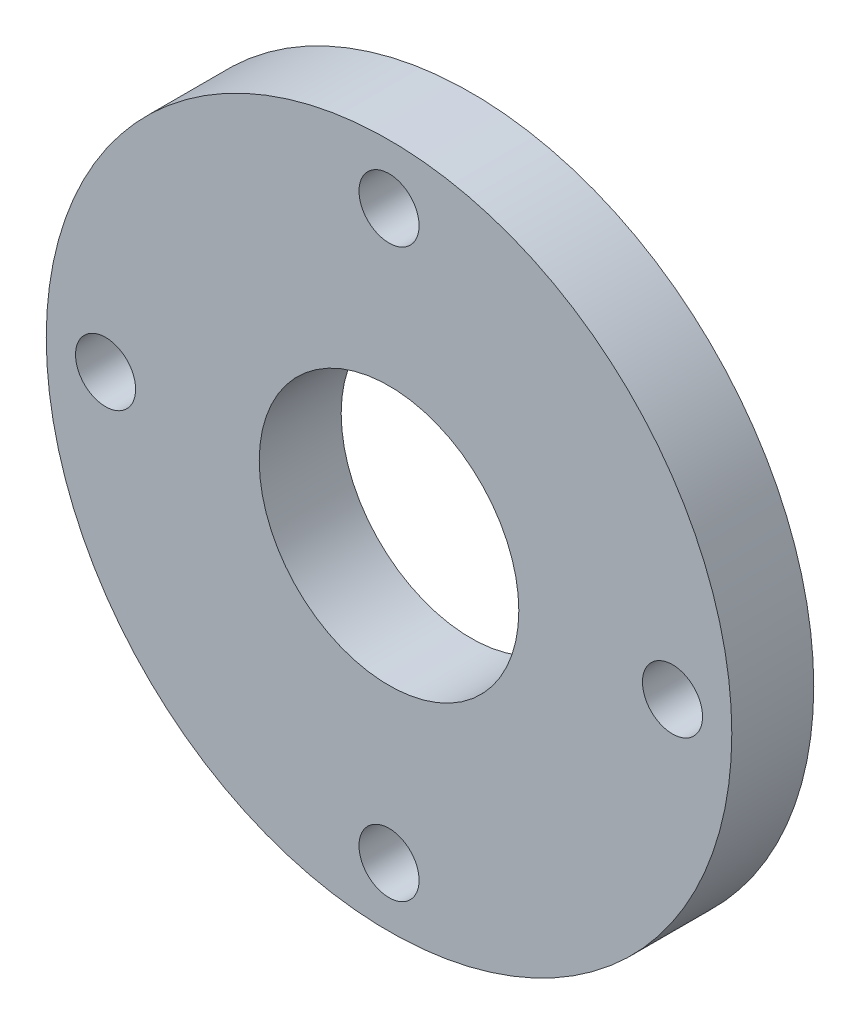
SolidWorks part; units mm, degrees
ref_plane "Front Plane" through (0, 0, 0) normal (0, 0, 1) x (1, 0, 0)
ref_plane "Top Plane" through (0, 0, 0) normal (0, 1, 0) x (1, 0, 0)
ref_plane "Right Plane" through (0, 0, 0) normal (1, 0, 0) x (0, 0, -1)
sketch "Sketch1" plane through (0, 0, 0) normal (1, 0, 0) x (0, 0, -1)
  line L0 (-103, -9.5) -> (-149, -9.5)
  line L5 (-1000, 0) -> (49000, 0)
  line L6 (0, -9.5) -> (0, 9.5)
  line L13 (0, 9.5) -> (-46.4, 9.5)
  line L26 (-46.4, 9.5) -> (-46.4, 14)
  line L27 (-46.4, 14) -> (-103, 14)
  line L32 (-103, 14) -> (-103, 9.5)
  line L34 (-165, 7) -> (-165, -7)
  line L36 (-103, -9.5) -> (-103, -14)
  line L37 (-103, -14) -> (-46.4, -14)
  line L38 (-46.4, -14) -> (-46.4, -9.5)
  line L39 (0, -9.5) -> (-46.4, -9.5)
  line L40 (-24.625, 37.6491) -> (-15.625, 37.6491)
  line L41 (-119.6, 22.6187) -> (-103, 22.6187)
  line L42 (-119.6, 22.6187) -> (-119.6, -22.6187)
  line L43 (-119.6, -22.6187) -> (-103, -22.6187)
  line L44 (-103, 22.6187) -> (-103, -22.6187)
  line L45 (-119.6, 22.6187) -> (-103, -22.6187) construction
  line L46 (-119.6, -22.6187) -> (-103, 22.6187) construction
  line L47 (-29.8, 22.6187) -> (-46.4, 22.6187)
  line L48 (-29.8, 22.6187) -> (-29.8, -22.6187)
  line L49 (-29.8, -22.6187) -> (-46.4, -22.6187)
  line L50 (-46.4, 22.6187) -> (-46.4, -22.6187)
  line L51 (-29.8, 22.6187) -> (-46.4, -22.6187) construction
  line L52 (-29.8, -22.6187) -> (-46.4, 22.6187) construction
  line L59 (-15.625, 37.6491) -> (-15.625, -37.6491)
  line L60 (-15.625, -37.6491) -> (-24.625, -37.6491)
  line L61 (-24.625, -22.6187) -> (-26.625, -22.6187)
  line L62 (-26.625, -22.6187) -> (-26.625, -12.5)
  line L63 (-26.625, -12.5) -> (-24.625, -12.5)
  line L64 (-24.625, -12.5) -> (-24.625, 12.5)
  line L65 (-24.625, 12.5) -> (-26.625, 12.5)
  line L66 (-26.625, 12.5) -> (-26.625, 22.6187)
  line L67 (-26.625, 22.6187) -> (-24.625, 22.6187)
  line L68 (-24.625, 22.6187) -> (-24.625, 37.6491)
  line L69 (-24.625, -22.6187) -> (-24.625, -37.6491)
  line L71 (-131.284, 37.6491) -> (-25.625, 37.6491)
  line L72 (-131.284, 37.6491) -> (-131.284, -37.6491)
  line L73 (-131.284, -37.6491) -> (-25.625, -37.6491)
  line L74 (-25.625, 37.6491) -> (-25.625, -37.6491)
  line L75 (-131.284, 37.6491) -> (-25.625, -37.6491) construction
  line L76 (-131.284, -37.6491) -> (-25.625, 37.6491) construction
  line L77 (-149, -9.5) -> (-149, -7)
  line L78 (-149, -7) -> (-165, -7)
  line L79 (-103, 9.5) -> (-149, 9.5)
  line L80 (-149, 7) -> (-165, 7)
  line L81 (-149, 9.5) -> (-149, 7)
  line L82 (-126, 9.5) -> (-126, -9.5) construction
  line L83 (-23.2, 9.5) -> (-23.2, -9.5) construction
  line L96 (-131.284, 37.6491) -> (-140.284, 37.6491)
  line L98 (-131.284, -37.6491) -> (-140.284, -37.6491)
  line L99 (-140.284, 37.6491) -> (-140.284, -37.6491)
  line L110 (-131.284, 37.6491) -> (-131.284, -37.6491)
  point P3 (0, 0)
  point P18 (-111.3, 0)
  point P24 (-38.1, 0)
  point P29 (-78.4545, 0)
  point P48 (-15.625, 31.1339)
  point P70 (-140.284, 31.1339)
revolve "Main_body" add sketch "Sketch1" angle 360 about L5 region at (0, 23.5746, 135.784)
sketch "Sketch5" plane through (0, 0, 140.284) normal (0, 0, 1) x (1, 0, 0)
  circle A0 centre (0, 0) radius 14.2558
  dimension "D1" = 28.5115
extrude "seal_seat" cut sketch "Sketch5" against normal through all
hole_wizard "M6 Clearance Hole1" positions "Sketch3" profile "Sketch4" hole size "M6" standard "ANSI Metric" end condition through all
sketch "Sketch3" plane through (0, 0, 140.284) normal (0, 0, 1) x (1, 0, 0)
  point P0 (0, 31.1339)
sketch "Sketch4" plane through (0, 31.1339, 140.284) normal (1, 0, 0) x (0, -1, 0)
  line L0 (0, 0) -> (0, 9)
  line L1 (0, 9) -> (3.3, 9)
  line L2 (3.3, 9) -> (3.3, 0)
  line L5 (3.3, 0) -> (0, 0)
  line L11 (0, -6.35) -> (0, 107.95) construction
  dimension "Thru Hole Dia." = 6.6
  dimension "Thru Hole Depth" = 9
pattern_circular "CirPattern1" count 4 over 360 about axis through (0, 0, 1000) along (0, 0, -1) of "M6 Clearance Hole1"
